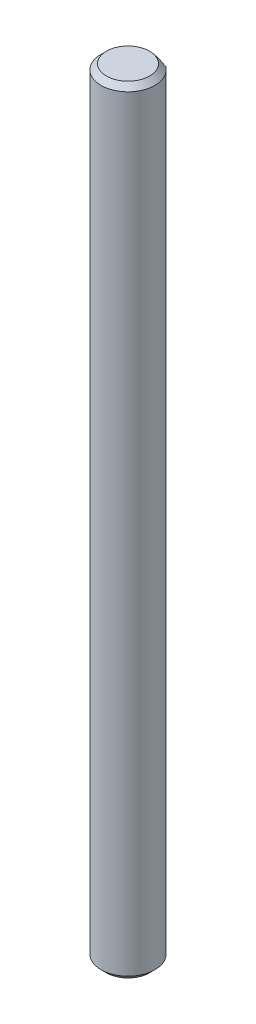
SolidWorks part; units mm, degrees
ref_plane "Спереди" through (0, 0, 0) normal (0, 0, 1) x (1, 0, 0)
ref_plane "Сверху" through (0, 0, 0) normal (0, 1, 0) x (1, 0, 0)
ref_plane "Справа" through (0, 0, 0) normal (1, 0, 0) x (0, 0, -1)
sketch "Эскиз1" plane through (0, 0, 0) normal (0, 1, 0) x (1, 0, 0)
  circle A0 centre (0, 0) radius 2.5
extrude "Бобышка-Вытянуть1" add sketch "Эскиз1" along normal blind 72
sketch "Эскиз2" plane through (0, 72, 0) normal (0, 1, 0) x (1, 0, 0)
  line L0 (0, -2.5) -> (-4.2999, -2.5) construction
  line L1 (-1.5, 2) -> (1.5, 2)
  circle A0 centre (0, 0) radius 2.5 construction
  arc A1 (1.5, 2) -> (-1.5, 2) centre (0, 0) ccw
  dimension "D1" = 4.5
  dimension "D2" = 5
extrude "Вырез-Вытянуть1" cut sketch "Эскиз2" against normal blind 15
chamfer "Фаска1" distance 0.5 angle 45 2 edges at (0, 72, 2.5) (0, 0, 2.5)
